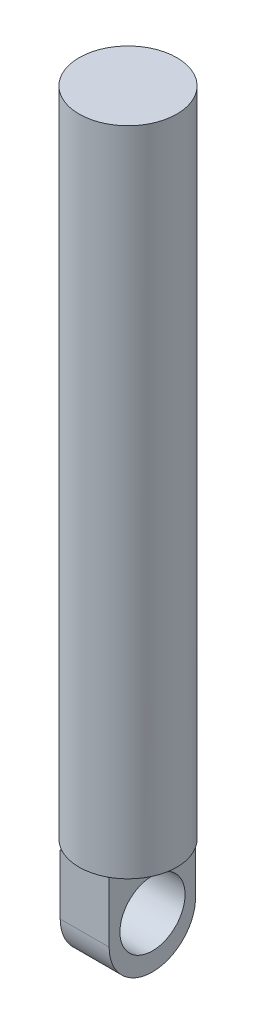
SolidWorks part; units mm, degrees
material "Cast Alloy Steel"
ref_plane "Front Plane" through (0, 0, 0) normal (0, 0, 1) x (1, 0, 0)
ref_plane "Top Plane" through (0, 0, 0) normal (0, 1, 0) x (1, 0, 0)
ref_plane "Right Plane" through (0, 0, 0) normal (1, 0, 0) x (0, 0, -1)
sketch "Sketch5" plane through (0, 0, 0) normal (0, 1, 0) x (1, 0, 0)
  circle A0 centre (0, 0) radius 14.9897
extrude "Boss-Extrude3" add sketch "Sketch5" along normal blind 200
ref_axis "Axis2" through (0, 210, 0) along (0, -1, 0)
ref_plane "Plane2" through (0, 0, 0) normal (-1, 0, 0) x (0, -1, 0)
sketch "Sketch6" plane through (0, 0, 0) normal (-1, 0, 0) x (0, -1, 0)
  line L2 (0, -14.9897) -> (0, 14.9897) construction
  line L3 (0, 13.2929) -> (18.3327, 13.2929)
  line L4 (17.6631, -13.2023) -> (0, -13.2023)
  line L5 (0, -13.2023) -> (0, 13.2929)
  circle A0 centre (16.6109, 0) radius 9.9749
  arc A1 (18.3327, 13.2929) -> (17.6631, -13.2023) centre (18.3327, 0.0368) cw
extrude "Boss-Extrude4" add sketch "Sketch6" along normal mid plane 15 contours L5 L3 A1 L4
sketch "Sketch7" plane through (7.5, 0, 0) normal (1, 0, 0) x (0, 0, -1)
  circle A0 centre (0, -15.9883) radius 9.9852
extrude "Cut-Extrude2" cut sketch "Sketch7" against normal mid plane 40
